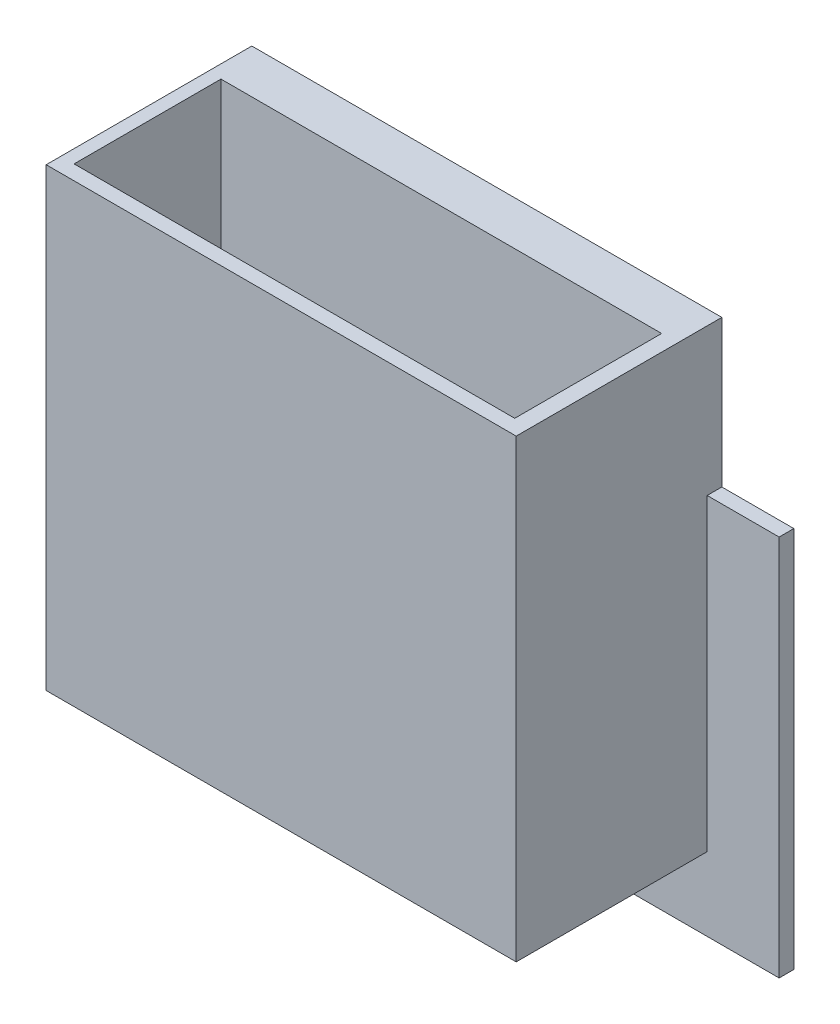
SolidWorks part; units mm, degrees
ref_plane "Front Plane" through (0, 0, 0) normal (0, 0, 1) x (1, 0, 0)
ref_plane "Top Plane" through (0, 0, 0) normal (0, 1, 0) x (1, 0, 0)
ref_plane "Right Plane" through (0, 0, 0) normal (1, 0, 0) x (0, 0, -1)
sketch "Sketch1" plane through (0, 0, 0) normal (0, 0, 1) x (1, 0, 0)
  line L0 (0, 0) -> (42, 0)
  line L1 (42, 0) -> (42, 26)
  line L2 (0, 0) -> (0, 26)
  line L3 (0, 26) -> (42, 26)
  line L4 (6, 26) -> (6, 36)
  line L5 (36, 26) -> (36, 36)
  line L6 (6, 36) -> (36, 36)
  line L7 (6, 26) -> (6, 6)
  line L8 (36, 26) -> (36, 6)
  line L9 (6, 6) -> (36, 6)
  line L10 (5.1, 26) -> (5.1, 4.9984)
  line L11 (5.1, 4.9984) -> (37.1, 4.9984)
  line L12 (37.1, 4.9984) -> (37.1, 26)
  line L13 (5.1, 26) -> (5.1, 36)
  line L14 (5.1, 36) -> (6, 36)
  line L15 (5.1, 36) -> (6, 36)
  line L16 (37.1, 26) -> (37.1, 36)
  line L17 (37.1, 36) -> (36, 36)
  point P11 (5.1, 26)
  dimension "D1" = 42
  dimension "D2" = 26
  dimension "D3" = 6
  dimension "D4" = 6
  dimension "D5" = 10
  dimension "D6" = 10
  dimension "D7" = 20
  dimension "D8" = 0.9
  dimension "D9" = 32
  dimension "D10" = 21.0016
extrude "Boss-Extrude1" add sketch "Sketch1" along normal blind 1 contours L12 L11 L10 L3 L2 L0 L1 region at (0.494, 13, 0)
extrude "Boss-Extrude2" add sketch "Sketch1<3>" along normal blind 14 contours L11 L12 L3 L8 L9 L7 L10 | L14 L13 L3 L4 | L16 L17 L5 L3 region at (5.55, 31, 0) region at (5.55, 25.6172, 0) region at (36.55, 31, 0)
sketch "Sketch1<3>" plane through (0, 0, 0) normal (0, 0, 1) x (1, 0, 0) same geometry as "Sketch1"
extrude "Boss-Extrude3" add sketch "Sketch1<4>" along normal blind 3 contours L6 L4 L3 L5 region at (21, 31, 0)
sketch "Sketch1<4>" plane through (0, 0, 0) normal (0, 0, 1) x (1, 0, 0) same geometry as "Sketch1"
sketch "Sketch2" plane through (0, 6, 0) normal (0, 1, 0) x (1, 0, 0)
  line L0 (6, -14) -> (6, -13)
  line L1 (6, -14) -> (6, -3) construction
  line L2 (36, -14) -> (36, -13)
  line L3 (36, -14) -> (36, 0) construction
  line L4 (6, -13) -> (36, -13)
  line L5 (6, -14) -> (36, -14)
  dimension "D1" = 1
extrude "Boss-Extrude4" add sketch "Sketch2" along normal blind 30
